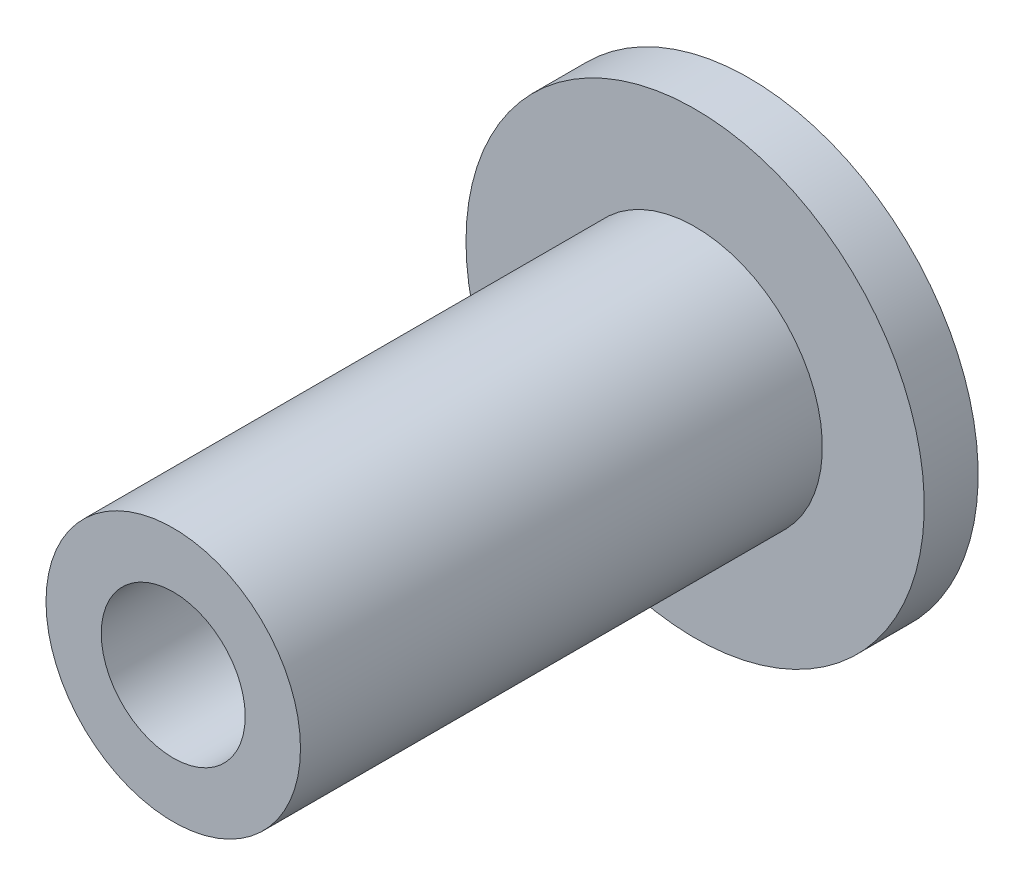
SolidWorks part; units mm, degrees
material "PLA2"
ref_plane "Front Plane" through (0, 0, 0) normal (0, 0, 1) x (1, 0, 0)
ref_plane "Top Plane" through (0, 0, 0) normal (0, 1, 0) x (1, 0, 0)
ref_plane "Right Plane" through (0, 0, 0) normal (1, 0, 0) x (0, 0, -1)
sketch "Sketch2" plane through (0, 0, 0) normal (0, 0, 1) x (1, 0, 0)
  line L1 (0, 0) -> (0, 50000) construction
  circle A1 centre (0, 0) radius 5.9944
  circle A4 centre (0, 0) radius 3.3909
  point P11 (0, 4.1275)
  dimension "D1" = 6.7818
  dimension "D3" = 11.9888
extrude "Boss-Extrude1" add sketch "Sketch2" along normal blind 10.033
sketch "Sketch4" plane through (0, 0, 10.033) normal (0, 0, -1) x (-1, 0, 0)
  circle A0 centre (0, 0) radius 3.3909 construction
  circle A1 centre (0, 0) radius 5.9944
  circle A2 centre (0, 0) radius 5.9944
  circle A3 centre (0, 0) radius 3.3909
  dimension "D1" = 0
sketch "Sketch6" plane through (0, 0, 0) normal (0, 1, 0) x (1, 0, 0)
  line L0 (-5.9944, 0) -> (-5.9944, 14.5542)
  line L1 (-5.9944, 14.5542) -> (-10.795, 14.5542)
  line L2 (-10.795, 14.5542) -> (-10.795, 17.0942)
  line L3 (-10.795, 17.0942) -> (-3.3909, 17.0942)
  line L4 (-3.3909, 17.0942) -> (-3.3909, 0)
  line L5 (-3.3909, 0) -> (-5.9944, 0)
  line L6 (0, 0) -> (0, -50000) construction
  line L7 (5.9944, 0) -> (-5.9944, 0) construction
  line L8 (5.9944, -10.033) -> (-5.9944, -10.033) construction
  point P13 (0, 0)
  dimension "D1" = 6.7818
  dimension "D2" = 24.5872
  dimension "D3" = 2.54
  dimension "D4" = 21.59
revolve "Revolve1" add sketch "Sketch6" angle 360 about L6
sketch "Sketch3" plane through (0, 0, 0) normal (0, -1, 0) x (1, 0, 0)
  line L0 (-5.715, 1.3462) -> (49994.285, 1.3462) construction
  line L3 (0, 0) -> (0, 2.6924) construction
  line L4 (10.795, -14.5542) -> (-10.795, -14.5542) construction
  circle A0 centre (0, 1.3462) radius 2.4384
  dimension "D1" = 4.8768
  dimension "D2" = 15.9004
extrude "Cut-Extrude1" cut sketch "Sketch3" along normal through all
